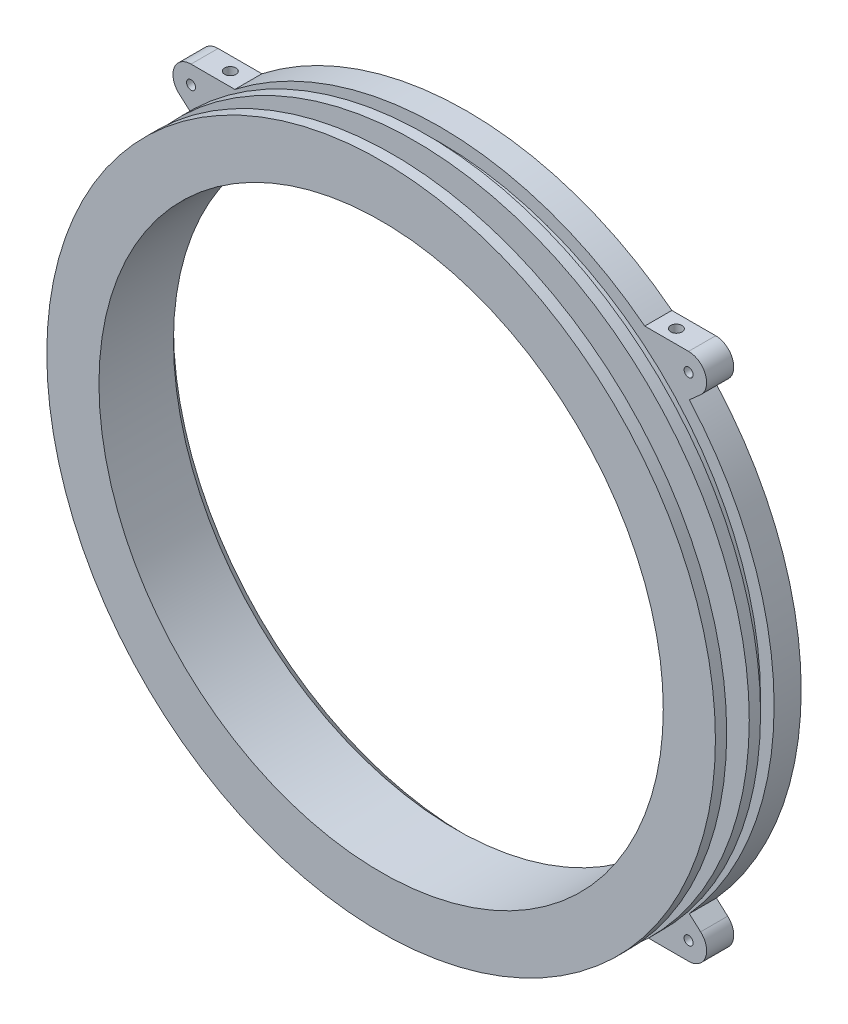
SolidWorks part; units mm, degrees
ref_plane "前视基准面" through (0, 0, 0) normal (0, 0, 1) x (1, 0, 0)
ref_plane "上视基准面" through (0, 0, 0) normal (0, 1, 0) x (1, 0, 0)
ref_plane "右视基准面" through (0, 0, 0) normal (1, 0, 0) x (0, 0, -1)
sketch "草图1" plane through (0, 0, 0) normal (0, 0, 1) x (1, 0, 0)
  circle A0 centre (0, 0) radius 148.1
  circle A1 centre (0, 0) radius 125
  dimension "D1" = 296.2
  dimension "D2" = 250
extrude "凸台-拉伸1" add sketch "草图1" along normal blind 12
sketch "草图2" plane through (0, 0, 12) normal (0, 0, 1) x (1, 0, 0)
  circle A0 centre (0, 0) radius 125
  circle A1 centre (0, 0) radius 142.1
  circle A2 centre (0, 0) radius 125 construction
  circle A3 centre (0, 0) radius 148.1 construction
  dimension "D1" = 6
extrude "凸台-拉伸2" add sketch "草图2" along normal blind 6
sketch "草图3" plane through (0, 0, 18) normal (0, 0, 1) x (1, 0, 0)
  circle A0 centre (0, 0) radius 125
  circle A1 centre (0, 0) radius 148.1
  circle A2 centre (0, 0) radius 125 construction
  circle A3 centre (0, 0) radius 148.1 construction
extrude "凸台-拉伸3" add sketch "草图3" along normal blind 5
sketch "草图4" plane through (0, 0, 23) normal (0, 0, 1) x (1, 0, 0)
  circle A0 centre (0, 0) radius 125
  circle A1 centre (0, 0) radius 133.1
  circle A2 centre (0, 0) radius 148.1 construction
  circle A4 centre (0, 0) radius 125 construction
  dimension "D1" = 15
extrude "凸台-拉伸4" add sketch "草图4" along normal blind 10
sketch "草图5" plane through (0, 0, 33) normal (0, 0, 1) x (1, 0, 0)
  circle A0 centre (0, 0) radius 125
  circle A1 centre (0, 0) radius 148.1
  circle A2 centre (0, 0) radius 125 construction
  circle A3 centre (0, 0) radius 148.1 construction
extrude "凸台-拉伸5" add sketch "草图5" along normal blind 5
sketch "草图6" plane through (0, 0, 0) normal (0, 0, 1) x (1, 0, 0)
  line L0 (-90.7998, 117) -> (-110.2082, 117)
  line L1 (-115.5327, 103.0293) -> (-110.5327, 98.5704)
  line L2 (0, 35.2925) -> (0, -26.8494) construction
  line L3 (-23.0779, 0) -> (26.357, 0) construction
  line L4 (115.5327, 103.0293) -> (110.5327, 98.5704)
  line L5 (90.7998, 117) -> (110.2082, 117)
  line L6 (115.5327, -103.0293) -> (110.5327, -98.5704)
  line L7 (90.7998, -117) -> (110.2082, -117)
  line L8 (-115.5327, -103.0293) -> (-110.5327, -98.5704)
  line L9 (-90.7998, -117) -> (-110.2082, -117)
  circle A0 centre (0, 0) radius 148.1 construction
  arc A1 (-110.2082, 117) -> (-115.5327, 103.0293) centre (-110.2082, 109) ccw
  arc A2 (-110.5327, 98.5704) -> (-90.7998, 117) centre (0, 0) cw
  circle A3 centre (-110.2082, 109) radius 2
  circle A4 centre (110.2082, 109) radius 2
  arc A5 (110.5327, 98.5704) -> (90.7998, 117) centre (0, 0) ccw
  arc A6 (110.2082, 117) -> (115.5327, 103.0293) centre (110.2082, 109) cw
  circle A7 centre (110.2082, -109) radius 2
  arc A8 (110.2082, -117) -> (115.5327, -103.0293) centre (110.2082, -109) ccw
  arc A9 (110.5327, -98.5704) -> (90.7998, -117) centre (0, 0) cw
  circle A10 centre (-110.2082, -109) radius 2
  arc A11 (-110.5327, -98.5704) -> (-90.7998, -117) centre (0, 0) ccw
  arc A12 (-110.2082, -117) -> (-115.5327, -103.0293) centre (-110.2082, -109) cw
  dimension "D1" = 4
  dimension "D2" = 8
  dimension "D3" = 5
  dimension "D4" = 117
extrude "凸台-拉伸6" add sketch "草图6" along normal blind 12
sketch "草图7" plane through (0, 117, 0) normal (0, 1, 0) x (1, 0, 0)
  line L0 (-90.7998, 0) -> (-110.2082, 0) construction
  line L2 (-90.7998, -12) -> (-90.7998, 0) construction
  circle A0 centre (-98.7998, -6) radius 2.5
  dimension "D1" = 5
  dimension "D2" = 6
  dimension "D3" = 8
extrude "切除-拉伸1" cut sketch "草图7" against normal blind 15
cosmetic thread "装饰螺纹线1" parameters "D2"=6
mirror "镜向1" about plane through (0, 0, 0) normal (1, 0, 0) of "切除-拉伸1"
mirror "镜向2" about plane through (0, 0, 0) normal (0, 1, 0) of "镜向1"
chamfer "倒角1" distance 5 angle 45 1 edges at (125, 0, 0)
